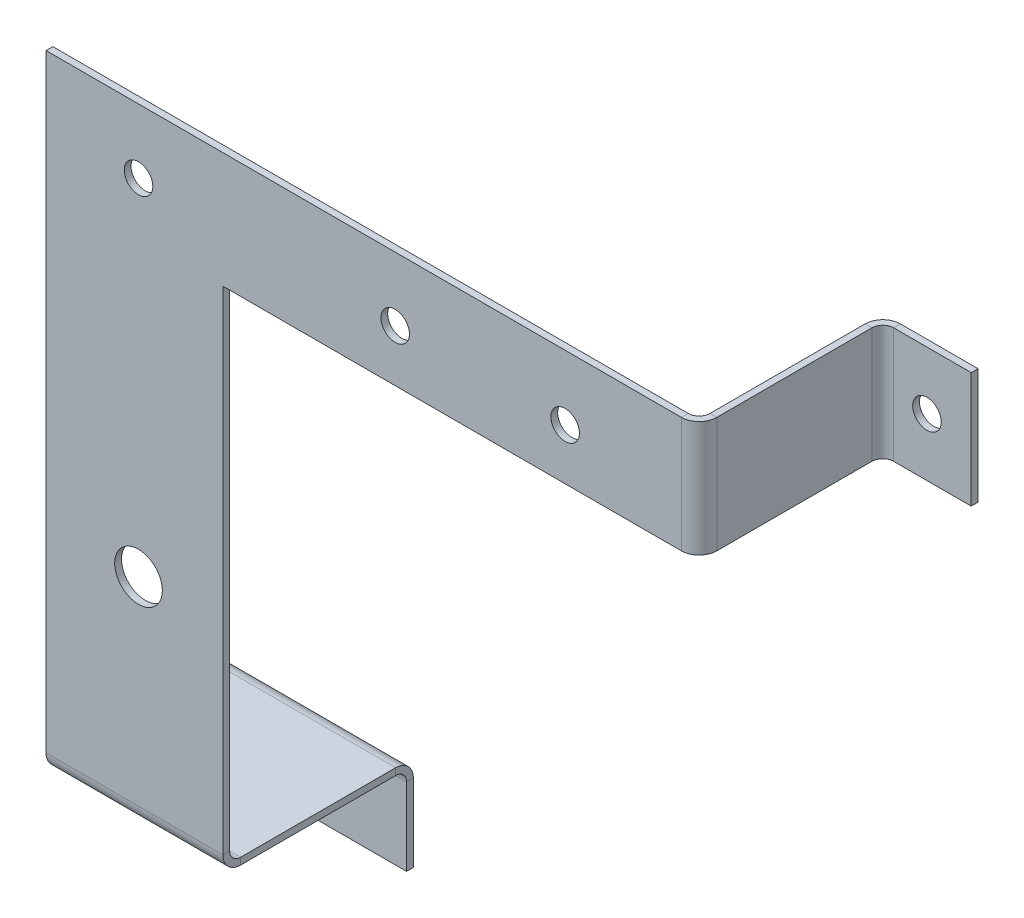
SolidWorks part; units mm, degrees
note: The reader was unsure of these and kept them because the rebuilt part matched: flange length of "Edge-Flange1", "Edge-Flange2", "Edge-Flange3", "Edge-Flange4".
material "Plain Carbon Steel"
ref_plane "Front Plane" through (0, 0, 0) normal (0, 0, 1) x (1, 0, 0)
ref_plane "Top Plane" through (0, 0, 0) normal (0, 1, 0) x (1, 0, 0)
ref_plane "Right Plane" through (0, 0, 0) normal (1, 0, 0) x (0, 0, -1)
sketch "Sketch1" plane through (0, 0, 0) normal (0, 0, 1) x (1, 0, 0)
  line L0 (0, 0) -> (0, 17)
  line L1 (0, 0) -> (-70, 0)
  line L2 (0, 17) -> (-96, 17)
  line L3 (-96, 17) -> (-96, -75)
  line L4 (-70, 0) -> (-70, -75)
  line L5 (-70, -75) -> (-96, -75)
  dimension "D1" = 17
  dimension "D2" = 70
  dimension "D3" = 96
  dimension "D4" = 92
base flange "Base-Flange1" sketch "Sketch1" thickness 1 reverse thickness direction no parameters "D1"=1.6
edge flange "Edge-Flange1" sketch "Sketch8" flange angle 90 flange length 28 flange position material inside bend radius 1.6 thickness 1 relief rectangular parameters "D6"=10
sketch "Sketch8" plane through (0, 0, -1) normal (1, 0, 0) x (0, -1, 0)
  line L0 (0, 0) -> (-17, 0) construction
  line L1 (0, 0) -> (-17, 0)
  line L2 (-17, 0) -> (-17, 27)
  line L3 (-17, 27) -> (0, 27)
  line L4 (0, 27) -> (0, 0)
bend "EdgeBend1" bend radius 1.6 bend angle 90 parameters "D5"=1
edge flange "Edge-Flange2" sketch "Sketch11" flange angle 90 flange length 14 flange position material inside bend radius 1.6 thickness 1 relief rectangular parameters "D6"=10
sketch "Sketch11" plane through (0, 0, -28) normal (0, 0, -1) x (0, 1, 0)
  line L0 (0, 0) -> (17, 0) construction
  line L1 (0, 0) -> (17, 0)
  line L2 (0, 0) -> (0, 13)
  line L3 (0, 13) -> (17, 13)
  line L4 (17, 13) -> (17, 0)
bend "EdgeBend2" bend radius 1.6 bend angle 90 parameters "D5"=2
edge flange "Edge-Flange3" sketch "Sketch14" flange angle 90 flange length 28 flange position material inside bend radius 1.6 thickness 1 relief rectangular parameters "D6"=10
sketch "Sketch14" plane through (0, -75, -1) normal (0, -1, 0) x (-1, 0, 0)
  line L0 (96, 0) -> (70, 0) construction
  line L1 (96, 0) -> (70, 0)
  line L2 (70, 0) -> (70, 27)
  line L3 (70, 27) -> (96, 27)
  line L4 (96, 27) -> (96, 0)
bend "EdgeBend3" bend radius 1.6 bend angle 90 parameters "D5"=3
edge flange "Edge-Flange4" sketch "Sketch17" flange angle 90 flange length 14 flange position material inside bend radius 1.6 thickness 1 relief rectangular parameters "D6"=10
sketch "Sketch17" plane through (0, -75, -28) normal (0, 0, -1) x (1, 0, 0)
  line L0 (-96, 0) -> (-70, 0) construction
  line L1 (-96, 0) -> (-70, 0)
  line L2 (-96, 0) -> (-96, 13)
  line L3 (-96, 13) -> (-70, 13)
  line L4 (-70, 13) -> (-70, 0)
bend "EdgeBend4" bend radius 1.6 bend angle 90 parameters "D5"=4
sketch "Sketch18" plane through (0, 0, -27) normal (0, 0, 1) x (1, 0, 0)
  line L0 (6.5, 17) -> (6.5, 8.5)
  line L1 (13, 17) -> (0, 17) construction
  circle A0 centre (6.5, 8.5) radius 2.1
  dimension "D2" = 4.2
  dimension "D1" = 8.5
extrude "Cut-Extrude1" cut sketch "Sketch18" against normal blind 6
sketch "Sketch19" plane through (0, 0, 0) normal (0, 0, 1) x (1, 0, 0)
  line L0 (-96, -82.3) -> (-83, -82.3)
  line L1 (-96, -88) -> (-96, -76.6) construction
  circle A0 centre (-44.6724, 7.6116) radius 2.1
  circle A1 centre (-82.4015, 7.5382) radius 2.1
  circle A2 centre (-82.4015, -43.1987) radius 3.5
  circle A3 centre (-83, -82.3) radius 2.1
  circle A4 centre (-19.6876, 7.4891) radius 2.1
  dimension "D1" = 13
  dimension "D2" = 4.2
  dimension "D3" = 7
  dimension "D4" = 4.2
  dimension "D5" = 4.2
  dimension "D6" = 4.2
extrude "Cut-Extrude2" cut sketch "Sketch19" against normal blind 40
sketch "Sketch20" plane through (0, 0, 0) normal (0, 0, 1) x (1, 0, 0)
  circle A0 centre (-82.4015, -43.1987) radius 3.5
  dimension "D1" = 7
extrude "Cut-Extrude3" cut sketch "Sketch20" against normal blind 40 normal cut yes
sketch "Bend-Lines1" [suppressed] plane through (0, 0, 0) normal (0, 1, 0) x (1, 0, 0)
sketch "Bounding-Box1" [suppressed] plane through (0, 0, 0) normal (0, 1, 0) x (1, 0, 0)
sheet metal parameters "Sheet-Metal8" thickness 1 parameters "D1"=1.6
flat pattern "Flat-Pattern8" [suppressed]
sketch "Bend-Lines2" plane through (0, 0, 0) normal (0, 1, 0) x (1, 0, 0)
sketch3d "Bounding-Box2" [suppressed]
  line L0 (96, -72, 0) -> (0, -72, 0) construction
  line L1 (96, 17, 0) -> (0, 17, 0) construction
  line L2 (96, -72, 0) -> (96, 17, 0) construction
  line L3 (0, -72, 0) -> (0, 17, 0) construction
sheet metal parameters "Sheet-Metal9" thickness 1 parameters "D1"=1.6
flat pattern "Flat-Pattern8"
sketch "Bend-Lines2" plane through (0, 0, 0) normal (0, 0, 1) x (1, 0, 0)
  line L0 (-0.9507, 0) -> (-0.9507, 17) construction
  line L1 (-0.9507, 0) -> (-0.9507, 17) construction
sketch3d "Bounding-Box2" [suppressed]
  line L0 (-96, -72, 0) -> (25.0987, -72, 0) construction
  line L1 (-96, 17, 0) -> (25.0987, 17, 0) construction
  line L2 (-96, -72, 0) -> (-96, 17, 0) construction
  line L3 (25.0987, -72, 0) -> (25.0987, 17, 0) construction
bend of the flat pattern "Flatten-<EdgeBend1>1"
sheet metal parameters "Sheet-Metal10" thickness 1 parameters "D1"=1.6
flat pattern "Flat-Pattern8"
sketch "Bend-Lines2" plane through (0, 0, 0) normal (0, 0, 1) x (1, 0, 0)
  line L0 (-0.9507, 0) -> (-0.9507, 17) construction
  line L1 (-0.9507, 0) -> (-0.9507, 17) construction
  line L2 (25.148, 0) -> (25.148, 17) construction
  line L3 (25.148, 0) -> (25.148, 17) construction
sketch3d "Bounding-Box2" [suppressed]
  line L0 (-96, -75, 0) -> (38.1973, -75, 0) construction
  line L1 (-96, 17, 0) -> (38.1973, 17, 0) construction
  line L2 (-96, -75, 0) -> (-96, 17, 0) construction
  line L3 (38.1973, -75, 0) -> (38.1973, 17, 0) construction
bend of the flat pattern "Flatten-<EdgeBend1>1"
bend of the flat pattern "Flatten-<EdgeBend2>1"
sheet metal parameters "Sheet-Metal11" thickness 1 parameters "D1"=1.6
flat pattern "Flat-Pattern8"
sketch "Bend-Lines2" plane through (0, 0, 0) normal (0, 0, 1) x (1, 0, 0)
  line L0 (-0.9507, 0) -> (-0.9507, 17) construction
  line L1 (-0.9507, 0) -> (-0.9507, 17) construction
  line L2 (25.148, 0) -> (25.148, 17) construction
  line L3 (25.148, 0) -> (25.148, 17) construction
  line L4 (-96, -74.0493) -> (-70, -74.0493) construction
  line L5 (-96, -74.0493) -> (-70, -74.0493) construction
sketch3d "Bounding-Box2" [suppressed]
  line L0 (-96, -101.0987, 0) -> (38.1973, -101.0987, 0) construction
  line L1 (-96, 17, 0) -> (38.1973, 17, 0) construction
  line L2 (-96, -101.0987, 0) -> (-96, 17, 0) construction
  line L3 (38.1973, -101.0987, 0) -> (38.1973, 17, 0) construction
bend of the flat pattern "Flatten-<EdgeBend1>1"
bend of the flat pattern "Flatten-<EdgeBend2>1"
bend of the flat pattern "Flatten-<EdgeBend3>1"
sheet metal parameters "Sheet-Metal12" thickness 1 parameters "D1"=1.6
flat pattern "Flat-Pattern8"
sketch "Bend-Lines2" plane through (0, 0, 0) normal (0, 0, 1) x (1, 0, 0)
  line L0 (-0.9507, 0) -> (-0.9507, 17) construction
  line L1 (-0.9507, 0) -> (-0.9507, 17) construction
  line L2 (25.148, 0) -> (25.148, 17) construction
  line L3 (25.148, 0) -> (25.148, 17) construction
  line L4 (-96, -74.0493) -> (-70, -74.0493) construction
  line L5 (-96, -74.0493) -> (-70, -74.0493) construction
  line L6 (-96, -100.148) -> (-70, -100.148) construction
  line L7 (-96, -100.148) -> (-70, -100.148) construction
sketch3d "Bounding-Box2" [suppressed]
  line L0 (-96, -113.1973, 0) -> (38.1973, -113.1973, 0) construction
  line L1 (-96, 17, 0) -> (38.1973, 17, 0) construction
  line L2 (-96, -113.1973, 0) -> (-96, 17, 0) construction
  line L3 (38.1973, -113.1973, 0) -> (38.1973, 17, 0) construction
bend of the flat pattern "Flatten-<EdgeBend1>1"
bend of the flat pattern "Flatten-<EdgeBend2>1"
bend of the flat pattern "Flatten-<EdgeBend3>1"
bend of the flat pattern "Flatten-<EdgeBend4>1"
sheet metal parameters "Sheet-Metal13" thickness 1 parameters "D1"=1.6
flat pattern "Flat-Pattern8"
sketch "Bend-Lines2" plane through (0, 0, 0) normal (0, 0, 1) x (1, 0, 0)
  line L0 (-0.9507, 0) -> (-0.9507, 17) construction
  line L1 (-0.9507, 0) -> (-0.9507, 17) construction
  line L2 (25.148, 0) -> (25.148, 17) construction
  line L3 (25.148, 0) -> (25.148, 17) construction
  line L4 (-96, -74.0493) -> (-70, -74.0493) construction
  line L5 (-96, -74.0493) -> (-70, -74.0493) construction
  line L6 (-96, -100.148) -> (-70, -100.148) construction
  line L7 (-96, -100.148) -> (-70, -100.148) construction
sketch3d "Bounding-Box2" [suppressed]
  line L0 (-96, -113.1973, 0) -> (38.1973, -113.1973, 0) construction
  line L1 (-96, 17, 0) -> (38.1973, 17, 0) construction
  line L2 (-96, -113.1973, 0) -> (-96, 17, 0) construction
  line L3 (38.1973, -113.1973, 0) -> (38.1973, 17, 0) construction
bend of the flat pattern "Flatten-<EdgeBend1>1"
bend of the flat pattern "Flatten-<EdgeBend2>1"
bend of the flat pattern "Flatten-<EdgeBend3>1"
bend of the flat pattern "Flatten-<EdgeBend4>1"
sheet metal parameters "Sheet-Metal14" thickness 1 parameters "D1"=1.6
flat pattern "Flat-Pattern8"
sketch "Bend-Lines2" plane through (0, 0, 0) normal (0, 0, 1) x (1, 0, 0)
  line L0 (-0.9507, 0) -> (-0.9507, 17) construction
  line L1 (-0.9507, 0) -> (-0.9507, 17) construction
  line L2 (25.148, 0) -> (25.148, 17) construction
  line L3 (25.148, 0) -> (25.148, 17) construction
  line L4 (-96, -74.0493) -> (-70, -74.0493) construction
  line L5 (-96, -74.0493) -> (-70, -74.0493) construction
  line L6 (-96, -100.148) -> (-70, -100.148) construction
  line L7 (-96, -100.148) -> (-70, -100.148) construction
sketch3d "Bounding-Box2" [suppressed]
  line L0 (-96, -113.1973, 0) -> (38.1973, -113.1973, 0) construction
  line L1 (-96, 17, 0) -> (38.1973, 17, 0) construction
  line L2 (-96, -113.1973, 0) -> (-96, 17, 0) construction
  line L3 (38.1973, -113.1973, 0) -> (38.1973, 17, 0) construction
bend of the flat pattern "Flatten-<EdgeBend1>1"
bend of the flat pattern "Flatten-<EdgeBend2>1"
bend of the flat pattern "Flatten-<EdgeBend3>1"
bend of the flat pattern "Flatten-<EdgeBend4>1"
sheet metal parameters "Sheet-Metal15" thickness 1 parameters "D1"=1.6
flat pattern "Flat-Pattern8"
sketch "Bend-Lines2" plane through (0, 0, 0) normal (0, 0, 1) x (1, 0, 0)
  line L0 (-0.9507, 0) -> (-0.9507, 17) construction
  line L1 (-0.9507, 0) -> (-0.9507, 17) construction
  line L2 (25.148, 0) -> (25.148, 17) construction
  line L3 (25.148, 0) -> (25.148, 17) construction
  line L4 (-96, -74.0493) -> (-70, -74.0493) construction
  line L5 (-96, -74.0493) -> (-70, -74.0493) construction
  line L6 (-96, -100.148) -> (-70, -100.148) construction
  line L7 (-96, -100.148) -> (-70, -100.148) construction
sketch3d "Bounding-Box2" [suppressed]
  line L0 (-96, -113.1973, 0) -> (38.1973, -113.1973, 0) construction
  line L1 (-96, 17, 0) -> (38.1973, 17, 0) construction
  line L2 (-96, -113.1973, 0) -> (-96, 17, 0) construction
  line L3 (38.1973, -113.1973, 0) -> (38.1973, 17, 0) construction
bend of the flat pattern "Flatten-<EdgeBend1>1"
bend of the flat pattern "Flatten-<EdgeBend2>1"
bend of the flat pattern "Flatten-<EdgeBend3>1"
bend of the flat pattern "Flatten-<EdgeBend4>1"
